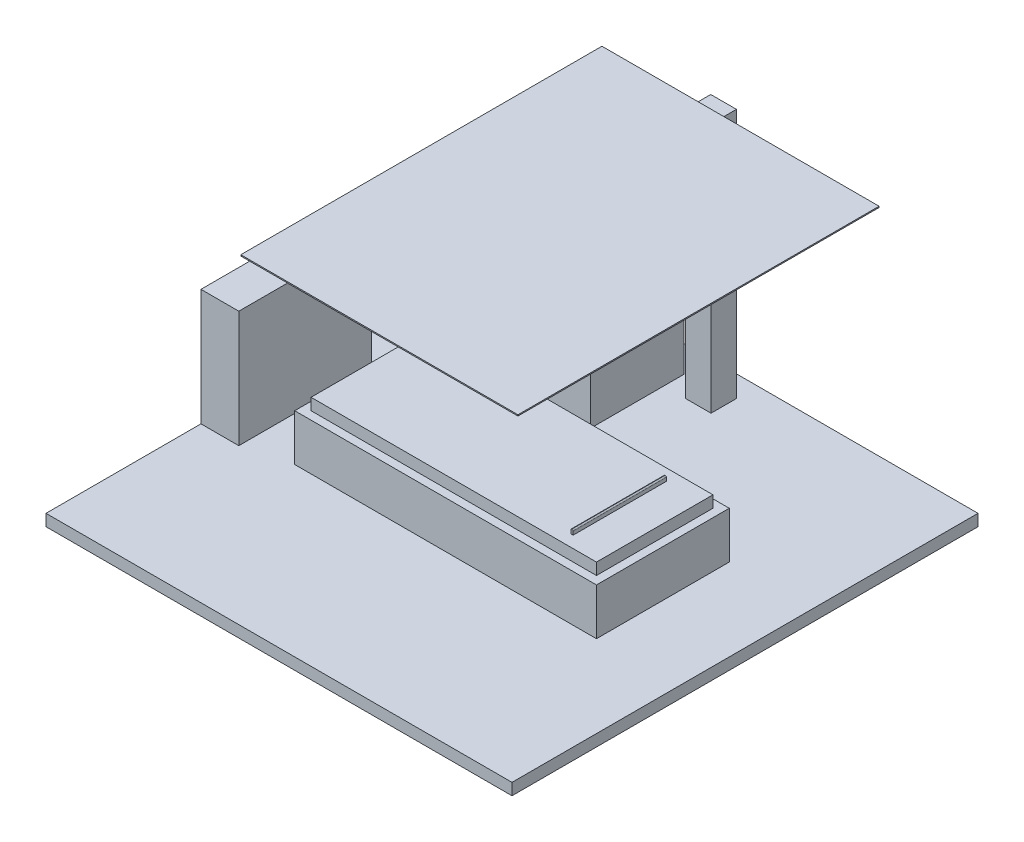
SolidWorks part; units mm, degrees
ref_plane "Front Plane" through (0, 0, 0) normal (0, 0, 1) x (1, 0, 0)
ref_plane "Top Plane" through (0, 0, 0) normal (0, 1, 0) x (1, 0, 0)
ref_plane "Right Plane" through (0, 0, 0) normal (1, 0, 0) x (0, 0, -1)
sketch "Sketch1" plane through (0, 0, 0) normal (0, 1, 0) x (1, 0, 0)
  line L1 (-2000, -2000) -> (2000, -2000)
  line L2 (-2000, -2000) -> (-2000, 2000)
  line L3 (-2000, 2000) -> (2000, 2000)
  line L4 (2000, -2000) -> (2000, 2000)
  line L5 (-2000, -2000) -> (2000, 2000) construction
  line L6 (-2000, 2000) -> (2000, -2000) construction
  point P0 (0, 0)
  dimension "D1" = 4000
  dimension "D2" = 4000
extrude "Boss-Extrude1" add sketch "Sketch1" along normal blind 100
sketch "Sketch2" plane through (0, 100, 0) normal (0, 1, 0) x (1, 0, 0)
  line L1 (-1295, -570) -> (1295, -570)
  line L2 (-1295, -570) -> (-1295, 570)
  line L3 (-1295, 570) -> (1295, 570)
  line L4 (1295, -570) -> (1295, 570)
  line L5 (-1295, -570) -> (1295, 570) construction
  line L6 (-1295, 570) -> (1295, -570) construction
  point P0 (0, 0)
  dimension "D1" = 2590
  dimension "D2" = 1140
extrude "Boss-Extrude2" add sketch "Sketch2" along normal blind 400
sketch "Sketch3" plane through (0, 500, 0) normal (0, 1, 0) x (1, 0, 0)
  line L1 (-1225, -500) -> (1225, -500)
  line L2 (-1225, -500) -> (-1225, 500)
  line L3 (-1225, 500) -> (1225, 500)
  line L4 (1225, -500) -> (1225, 500)
  line L5 (-1225, -500) -> (1225, 500) construction
  line L6 (-1225, 500) -> (1225, -500) construction
  point P0 (0, 0)
  dimension "D1" = 1000
  dimension "D2" = 2450
extrude "Boss-Extrude3" add sketch "Sketch3" along normal blind 100
sketch "Sketch4" plane through (0, 100, 0) normal (0, 1, 0) x (1, 0, 0)
  line L0 (-2000, 2000) -> (-2000, -2000) construction
  line L1 (-1295, 970) -> (-295, 970)
  line L2 (-1295, 970) -> (-1295, 1770)
  line L3 (-1295, 1770) -> (-295, 1770)
  line L4 (-295, 970) -> (-295, 1770)
  line L5 (-1295, 970) -> (-295, 1770) construction
  line L6 (-1295, 1770) -> (-295, 970) construction
  line L7 (-1675, -670) -> (-2000, -670)
  line L8 (-1675, -670) -> (-1675, 470)
  line L9 (-1675, 470) -> (-2000, 470)
  line L10 (-2000, -670) -> (-2000, 470)
  line L11 (-1675, -670) -> (-2000, 470) construction
  line L12 (-1675, 470) -> (-2000, -670) construction
  line L13 (1295, 570) -> (-1295, 570) construction
  line L14 (-1295, 570) -> (-1295, -570) construction
  line L15 (-1295, 570) -> (-1295, -570) construction
  point P0 (-795, 1370)
  point P5 (-1837.5, -100)
  dimension "D1" = 400
  dimension "D2" = 380
  dimension "D3" = 100
  dimension "D4" = 1140
  dimension "D5" = 1000
  dimension "D6" = 800
extrude "Boss-Extrude4" add sketch "Sketch4" along normal blind 1000
sketch "Sketch5" plane through (0, 100, 0) normal (0, 1, 0) x (1, 0, 0)
  line L1 (-110.2765, 1816.3242) -> (110.2765, 1816.3242)
  line L2 (-110.2765, 1816.3242) -> (-110.2765, 1598.2221)
  line L3 (-110.2765, 1598.2221) -> (110.2765, 1598.2221)
  line L4 (110.2765, 1816.3242) -> (110.2765, 1598.2221)
  line L5 (-110.2765, 1816.3242) -> (110.2765, 1598.2221) construction
  line L6 (-110.2765, 1598.2221) -> (110.2765, 1816.3242) construction
  point P0 (0, 1707.2732)
extrude "Boss-Extrude5" add sketch "Sketch5" along normal blind 2150
sketch "Sketch6" plane through (0, 0, -1598.2221) normal (0, 0, 1) x (1, 0, 0)
  line L1 (1452.7379, 2250) -> (-926.1899, 2250)
  line L2 (1452.7379, 2250) -> (1452.7379, 2260)
  line L3 (1452.7379, 2260) -> (-926.1899, 2260)
  line L4 (-926.1899, 2250) -> (-926.1899, 2260)
  dimension "D1" = 10
extrude "Boss-Extrude6" add sketch "Sketch6" along normal blind 3000 and the other way blind 100
sketch "Sketch7" plane through (0, 600, 0) normal (0, 1, 0) x (1, 0, 0)
  line L0 (1225, -500) -> (1225, 500) construction
  line L1 (925, 400) -> (905, 400)
  line L2 (925, 400) -> (925, -400)
  line L3 (925, -400) -> (905, -400)
  line L4 (905, 400) -> (905, -400)
  line L5 (-1225, -500) -> (1225, -500) construction
  dimension "D1" = 20
  dimension "D2" = 300
  dimension "D3" = 800
  dimension "D4" = 100
extrude "Boss-Extrude7" add sketch "Sketch7" along normal blind 40
fillet "Fillet1" radius 10 2 edges at (925, 640, 0) (905, 640, 0)
